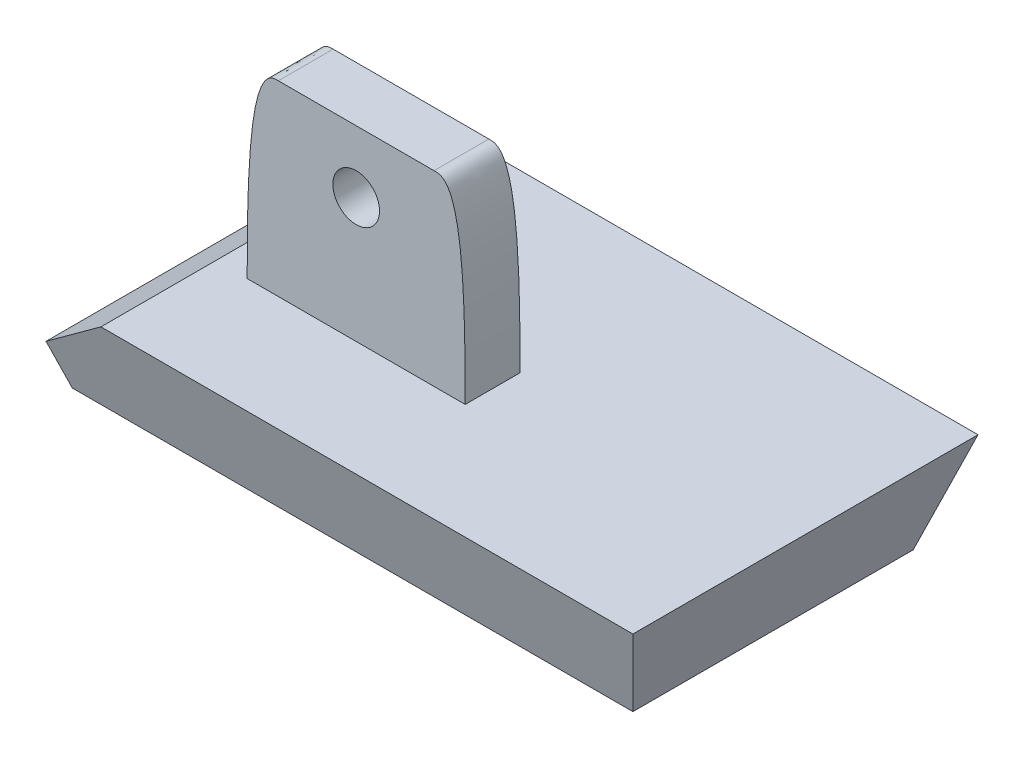
SolidWorks part; units mm, degrees
ref_plane "Ebene vorne" through (0, 0, 0) normal (0, 0, 1) x (1, 0, 0)
ref_plane "Ebene oben" through (0, 0, 0) normal (0, 1, 0) x (1, 0, 0)
ref_plane "Ebene rechts" through (0, 0, 0) normal (1, 0, 0) x (0, 0, -1)
sketch "Skizze1" plane through (0, 0, 0) normal (0, 1, 0) x (1, 0, 0)
  line L1 (-90, -45) -> (90, -45)
  line L2 (-90, -45) -> (-90, 45)
  line L3 (-90, 45) -> (90, 45)
  line L4 (90, -45) -> (90, 45)
  line L5 (-90, -45) -> (90, 45) construction
  line L6 (-90, 45) -> (90, -45) construction
  point P0 (0, 0)
  dimension "D1" = 180
  dimension "D2" = 90
extrude "Aufsatz-Linear austragen1" add sketch "Skizze1" along normal blind 32 draft 18 draft outward yes
sketch "Skizze2" plane through (0, 32, 0) normal (0, 1, 0) x (1, 0, 0)
  line L1 (-60.3451, -0.8985) -> (9.6549, -0.8985)
  line L2 (-60.3451, -0.8985) -> (-60.3451, -18.4986)
  line L3 (-60.3451, -18.4986) -> (9.6549, -18.4986)
  line L4 (9.6549, -0.8985) -> (9.6549, -18.4986)
  dimension "D1" = 70
extrude "Aufsatz-Linear austragen2" add sketch "Skizze2" along normal blind 60
sketch "Skizze3" plane through (0, 0, 0.8985) normal (0, 0, -1) x (-1, 0, 0)
  line L0 (-9.6549, 32) -> (60.3451, 32) construction
  circle A0 centre (25.3451, 72) radius 7.5
  point P4 (25.3451, 32)
  point P5 (25.3451, 68.8148)
  dimension "D1" = 15
  dimension "D2" = 40
extrude "Schnitt-Linear austragen1" cut sketch "Skizze3" against normal up to surface (17.6001 mm away) up to face at (-25.3451, 62, 18.4986)
fillet "Verrundung1" radius 60 2 edges at (9.6549, 92, 9.6985) (-60.3451, 92, 9.6985) curvature continuous yes second distance 10 first distance on face at (9.6549, 62, 9.6985) first distance on face at (-60.3451, 62, 9.6985)
chamfer "Fase1" distance 20 distance2 30 1 edges at (-100.3974, 32, 0) first distance on face at (-95.1987, 16, 0)
